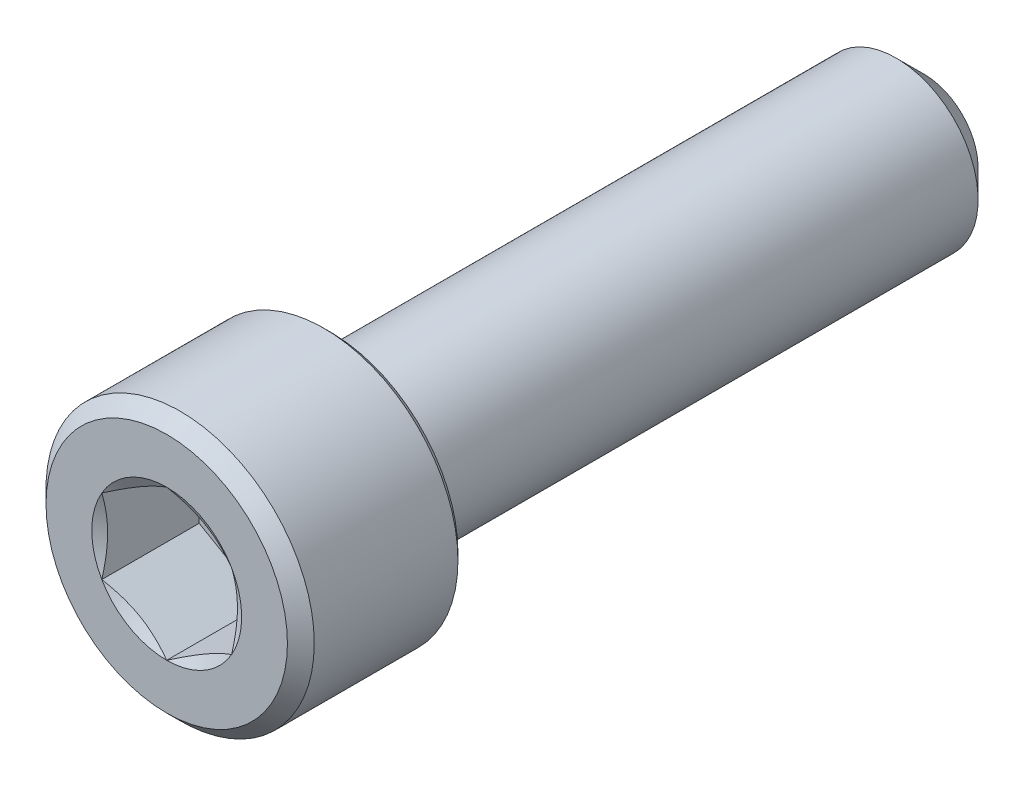
SolidWorks part; units mm, degrees
ref_plane "Front Plane" through (0, 0, 0) normal (0, 0, 1) x (1, 0, 0)
ref_plane "Top Plane" through (0, 0, 0) normal (0, 1, 0) x (1, 0, 0)
ref_plane "Right Plane" through (0, 0, 0) normal (1, 0, 0) x (0, 0, -1)
sketch "Sketch1" plane through (0, 0, 0) normal (1, 0, 0) x (0, 0, -1)
  line L0 (8.1026, 0) -> (-8.1026, 0) construction
  line L1 (-8.1026, 0) -> (-8.1026, 2.8702) construction
  line L2 (-4.5974, 1.7526) -> (-4.5974, 0) construction
  line L3 (7.3088, 0) -> (7.3088, 0.7938) construction
  line L4 (-4.5974, 0) -> (-4.5974, -1.7526) construction
  line L5 (8.1026, 1.7526) -> (8.1026, -1.7526) construction
  line L6 (-4.5974, 1.7526) -> (-4.5974, 2.8702) construction
  point P6 (-8.1026, 1.3891)
  point P9 (-8.1026, -1.3891)
  point P10 (-4.5974, 0)
  point P13 (5.3245, -1.7526)
  dimension "Head Diameter" = 5.7404
  dimension "Head Height" = 3.5052
  dimension "Screw Size Decimal Equivalent" = 3.5052
  dimension "Length" = 12.7
  dimension "Pitch" = 0.7937
  dimension "Drive Size" = 2.7781
  dimension "D1" = 0.7937
  dimension "D2" = 2.7781
sketch "Sketch2" plane through (0, 0, 0) normal (1, 0, 0) x (0, 0, -1)
  line L0 (8.1026, 1.1573) -> (7.5073, 1.7526)
  line L1 (-8.1026, 2.8702) -> (-4.5974, 2.8702)
  line L2 (-8.1026, 2.8702) -> (-8.1026, 0)
  line L4 (-4.5974, 2.8702) -> (-4.5974, 1.7526)
  line L5 (-4.5974, 1.7526) -> (7.5073, 1.7526)
  line L8 (8.1026, 1.1573) -> (8.1026, 0)
  line L9 (8.1026, 0) -> (-8.1026, 0) construction
  line L10 (8.1026, 0) -> (-8.1026, 0)
  dimension "D1" = 135
  dimension "D2" = 0.5953
revolve "Revolve1" add sketch "Sketch2" angle 360 about L10
sketch "Sketch4" plane through (0, 0, 8.1026) normal (0, 0, 1) x (1, 0, 0)
  line L1 (0, 1.604) -> (-1.3891, 0.802)
  line L2 (-1.3891, 0.802) -> (-1.3891, -0.802)
  line L3 (-1.3891, -0.802) -> (0, -1.604)
  line L4 (0, -1.604) -> (1.3891, -0.802)
  line L5 (1.3891, -0.802) -> (1.3891, 0.802)
  line L6 (1.3891, 0.802) -> (0, 1.604)
  circle A0 centre (0, 0) radius 1.3891 construction
  circle A1 centre (0, 0) radius 2.8702 construction
  circle A2 centre (0, 0) radius 2.8702 construction
  dimension "D1" = 2.7781
extrude "Cut-Extrude1" cut sketch "Sketch4" against normal blind 2.0836
sketch "Sketch5" plane through (0, 0, 8.1026) normal (0, 0, 1) x (1, 0, 0)
  circle A0 centre (0, 0) radius 1.604
extrude "Cut-Extrude2" cut sketch "Sketch5" against normal blind 10 draft 60
chamfer "Chamfer1" distance 0.287 angle 45 1 edges at (-2.8702, 0, 8.1026)
chamfer "Chamfer2" distance 0.1435 angle 45 1 edges at (-2.8702, 0, 4.5974)
sketch "Sketch3" [suppressed] plane through (0, 0, -8.1026) normal (0, 0, -1) x (-1, 0, 0)
  circle A0 centre (0, 0) radius 1.7526 construction
  circle A1 centre (0, 0) radius 1.7526
ref_axis "Center Axis1" through (0, 0, -5.7305) along (0, 0, 1)
ref_plane "Contact Plane1" through (0, 0, -8.1026) normal (0, 0, 1) x (1, 0, 0)
ref_plane "Contact Plane2" through (0, 0, 4.5974) normal (0, 0, 1) x (1, 0, 0)
ref_plane "Plane1" [suppressed] through (0, 0, 4.4982) normal (0, 0, -1) x (-1, 0, 0)
split "Split1" [suppressed] bodies to split 106
curve "Helix/Spiral1" [suppressed] pitch 0.7937 height 13.4937 turns 17
sketch "Sketch7" [suppressed] plane through (0, 0, 0) normal (1, 0, 0) x (0, 0, -1)
  line L0 (8.053, 1.8385) -> (8.4499, 1.1511) construction
  line L1 (8.4499, 1.1511) -> (8.8467, 1.8385) construction
  line L2 (8.8467, 1.8385) -> (8.053, 1.8385) construction
  line L3 (8.1026, 1.7526) -> (8.7971, 1.7526)
  line L4 (8.4499, 1.8385) -> (8.4499, 1.7526) construction
  line L5 (8.4499, 1.7526) -> (8.4499, 1.237) construction
  line L6 (8.4499, 1.237) -> (8.4499, 1.1511) construction
  line L7 (8.4003, 1.237) -> (8.4995, 1.237)
  line L9 (8.4995, 1.237) -> (8.7971, 1.7526)
  line L10 (8.4003, 1.237) -> (8.1026, 1.7526)
  line L11 (7.3088, 0) -> (7.3088, 0.7938) construction
  line L13 (8.1026, -1.7526) -> (8.1026, 1.7526)
  line L14 (8.1026, -1.7526) -> (8.1026, 1.7526) construction
  dimension "D2" = 0.0992
sweep "Cut-Sweep1" [suppressed] cut profiles "Sketch7" path "Helix/Spiral1"
sketch "Sketch12" [suppressed] plane through (0, 0, 4.4982) normal (0, 0, -1) x (-1, 0, 0)
  circle A0 centre (0, 0) radius 1.832
  circle A1 centre (0, 0) radius 1.7526
  circle A2 centre (0, 0) radius 1.7526 construction
  dimension "D2" = 0.0794
extrude "Boss-Extrude5" [suppressed] add sketch "Sketch12" against normal up to surface (0.0992 mm away)
sketch "Sketch11" [suppressed] plane through (0, 0, 4.4982) normal (0, 0, -1) x (-1, 0, 0)
  circle A2 centre (0, 0) radius 1.832
  circle A3 centre (0, 0) radius 1.832
  dimension "D1" = 0
extrude "Boss-Extrude4" [suppressed] add sketch "Sketch11" along normal through all draft 59.977
sketch "Sketch9" [suppressed] plane through (0, 0, 4.5974) normal (0, 0, -1) x (-1, 0, 0)
  line L0 (0, 0) -> (0, 2.8702) construction
  line L1 (0, 2.7267) -> (-0.3008, 3.0137)
  line L2 (-0.3008, 3.0137) -> (0.3008, 3.0137)
  line L3 (0.3008, 3.0137) -> (0, 2.7267)
  line L4 (-0.1504, 2.8702) -> (0, 0) construction
  line L5 (0, 0) -> (0.1504, 2.8702) construction
  circle A0 centre (0, 0) radius 2.8702 construction
  circle A1 centre (0, 0) radius 2.7267 construction
  dimension "D1" = 0.287
  dimension "D2" = 6
extrude "Cut-Extrude3" [suppressed] cut sketch "Sketch9" against normal up to next
pattern_circular "CirPattern1" [suppressed] count 60 over 360 of bodies 112
equation "\"Pitch Natural Taper Angle\"= ATN ( \"Pitch@Sketch1\" / 2 )"
equation "\"Rounded Angle Count\"= ROUND ( 60 / \"Pitch Natural Taper Angle\" )"
equation "\"Taper Angle\"= \"Rounded Angle Count\" * \"Pitch Natural Taper Angle\""
equation "\"D1@Sketch1\"=\"Pitch@Sketch1\""
equation "\"D2@Sketch2\"=\"D1@Sketch1\"*.75"
equation "\"D4@Helix/Spiral1\"=\"Pitch@Sketch1\""
equation "\"D3@Helix/Spiral1\"=\"Length@Sketch1\"+\"Pitch@Sketch1\""
equation "\"D1@Sketch4\" = \"Drive Size@Sketch1\""
equation "\"D1@Cut-Extrude1\"=\"D1@Sketch4\"*.75"
equation "\"D1@Chamfer1\" = \"Head Diameter@Sketch1\" * .05"
equation "\"D1@Chamfer2\"=\"D1@Chamfer1\"/2"
equation "\"D2@Sketch7\"=\"Pitch@Sketch1\"*0.125"
equation "\"D2@Sketch1\"=\"Pitch@Sketch1\"*3.5"
equation "\"D1@Sketch9\"=\"D1@Chamfer1\""
equation "\"D1@CirPattern1\"=\"D3@CirPattern1\"/\"D2@Sketch9\""
equation "\"D1@Plane1\"=\"Pitch@Sketch1\"*0.125"
equation "\"D3@Boss-Extrude4\"=\"Taper Angle\""
equation "\"D2@Sketch12\"=\"Pitch@Sketch1\"*0.1"
